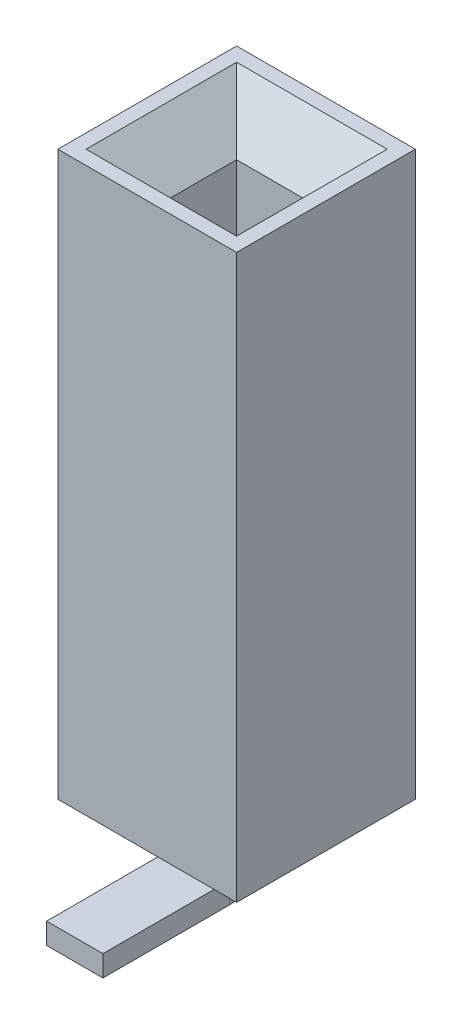
SolidWorks part; units mm, degrees
ref_plane "Alzado" through (0, 0, 0) normal (0, 0, 1) x (1, 0, 0)
ref_plane "Planta" through (0, 0, 0) normal (0, 1, 0) x (1, 0, 0)
ref_plane "Vista lateral" through (0, 0, 0) normal (1, 0, 0) x (0, 0, -1)
sketch "Sketch1" plane through (0, 0, 0) normal (0, 1, 0) x (1, 0, 0)
  line L1 (1.27, -1.27) -> (-1.27, -1.27)
  line L2 (1.27, -1.27) -> (1.27, 1.27)
  line L3 (1.27, 1.27) -> (-1.27, 1.27)
  line L4 (-1.27, -1.27) -> (-1.27, 1.27)
  line L5 (1.27, -1.27) -> (-1.27, 1.27) construction
  point P0 (0, 0)
  dimension "D1" = 2.54
extrude "Boss-Extrude1" add sketch "Sketch1" along normal blind 8
sketch "Sketch2" plane through (0, 8, 0) normal (0, 1, 0) x (1, 0, 0)
  line L8 (-0.47, 0.47) -> (-0.47, -0.47)
  line L9 (-0.47, -0.47) -> (0.47, -0.47)
  line L10 (0.47, -0.47) -> (0.47, 0.47)
  line L11 (0.47, 0.47) -> (-0.47, 0.47)
  line L12 (-0.47, 0.47) -> (-0.47, -0.47)
  line L13 (-0.47, -0.47) -> (0.47, -0.47)
  line L14 (0.47, -0.47) -> (0.47, 0.47)
  line L15 (0.47, 0.47) -> (-0.47, 0.47)
  dimension "D1" = 0.8
extrude "Cut-Extrude1" cut sketch "Sketch2" against normal blind 7
chamfer "Chamfer1" distance 0.6 angle 45 4 edges at (0.47, 8, 0) (0, 8, 0.47) (-0.47, 8, 0) (0, 8, -0.47)
sketch "Sketch3" plane through (0, 0, 0) normal (0, -1, 0) x (1, 0, 0)
  line L1 (0.4, -0.15) -> (-0.4, -0.15)
  line L2 (0.4, -0.15) -> (0.4, 0.15)
  line L3 (0.4, 0.15) -> (-0.4, 0.15)
  line L4 (-0.4, -0.15) -> (-0.4, 0.15)
  line L5 (0.4, -0.15) -> (-0.4, 0.15) construction
  line L6 (0.4, 0.15) -> (-0.4, -0.15) construction
  point P0 (0, 0)
  dimension "D1" = 0.8
  dimension "D2" = 0.3
ref_plane "Plane1" through (0, 0, 0) normal (-1, 0, 0) x (0, 0, 1)
sketch "Sketch4" plane through (0, 0, 0) normal (-1, 0, 0) x (0, 0, 1)
  line L0 (0, 0) -> (0, -0.2)
  line L1 (0.5, -0.7) -> (2.3, -0.7)
  arc A0 (0, -0.2) -> (0.5, -0.7) centre (0.5, -0.2) ccw
  point P6 (0, -0.7)
  dimension "D3" = 0.5
  dimension "D1" = 0.7
  dimension "D2" = 2.3
sweep "Sweep1" add profiles "Sketch3" path "Sketch4"
ref_plane "Plane2" through (0, -0.7, 0) normal (0, -1, 0) x (-1, 0, 0)
ref_axis "Pin Axis" through (0, -0.7, 0.0519) along (0, 0, 1)
ref_axis "Plug Axis" through (0, 8.4425, 0) along (0, -1, 0)
